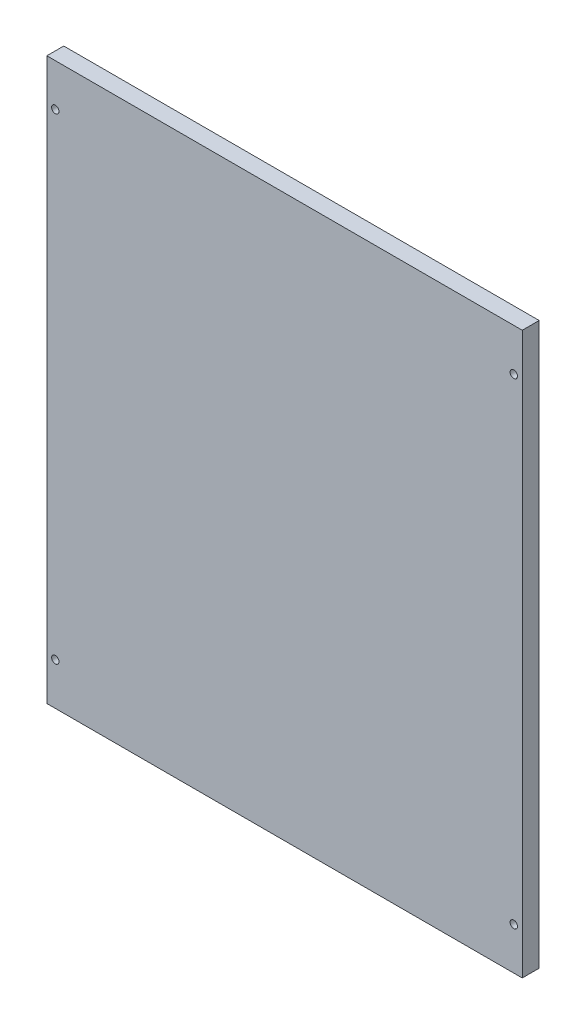
SolidWorks part; units mm, degrees
material "ДСП"
ref_plane "Спереди" through (0, 0, 0) normal (0, 0, 1) x (1, 0, 0)
ref_plane "Сверху" through (0, 0, 0) normal (0, 1, 0) x (1, 0, 0)
ref_plane "Справа" through (0, 0, 0) normal (1, 0, 0) x (0, 0, -1)
sketch "Эскиз1" plane through (0, 0, 0) normal (0, 0, 1) x (1, 0, 0)
  line L1 (0, 0) -> (450, 0)
  line L2 (0, 0) -> (0, 531)
  line L3 (0, 531) -> (450, 531)
  line L4 (450, 0) -> (450, 531)
  dimension "D1" = 531
  dimension "D2" = 450
extrude "Придание толщины" add sketch "Эскиз1" along normal blind 16
sketch "Эскиз3" plane through (0, 0, 16) normal (0, 0, 1) x (1, 0, 0)
  line L0 (0, 531) -> (0, 0) construction
  line L1 (0, 0) -> (450, 0) construction
  circle A0 centre (8, 40) radius 3.5
  dimension "D1" = 7
  dimension "D2" = 8
  dimension "D3" = 40
extrude "Отверстие 1" cut sketch "Эскиз3" against normal blind 16
sketch "Эскиз4" plane through (0, 0, 16) normal (0, 0, 1) x (1, 0, 0)
  line L0 (0, 531) -> (0, 0) construction
  line L1 (0, 0) -> (450, 0) construction
  circle A0 centre (8, 491) radius 3.5
  dimension "D3" = 7
  dimension "D1" = 8
  dimension "D2" = 491
extrude "Отверстие 2" cut sketch "Эскиз4" against normal blind 16
sketch "Эскиз5" plane through (0, 0, 16) normal (0, 0, 1) x (1, 0, 0)
  line L0 (0, 531) -> (0, 0) construction
  line L1 (0, 0) -> (450, 0) construction
  circle A0 centre (442, 40) radius 3.5
  dimension "D1" = 7
  dimension "D3" = 40
  dimension "D2" = 442
extrude "Отверстие 3" cut sketch "Эскиз5" against normal blind 16
sketch "Эскиз6" plane through (0, 0, 16) normal (0, 0, 1) x (1, 0, 0)
  line L0 (0, 531) -> (0, 0) construction
  line L1 (0, 0) -> (450, 0) construction
  circle A0 centre (442, 491) radius 3.5
  dimension "D1" = 7
  dimension "D2" = 442
  dimension "D3" = 491
extrude "Отверстие 4" cut sketch "Эскиз6" against normal blind 16
sketch "Эскиз7" plane through (0, 0, 16) normal (0, 0, 1) x (1, 0, 0)
  line L0 (0, 531) -> (0, 0) construction
  line L1 (0, 0) -> (450, 0) construction
  circle A0 centre (0, 0) radius 4
  dimension "D1" = 8
extrude "Отверстие 5" [suppressed] cut sketch "Эскиз7" against normal blind 16
sketch "Эскиз8" plane through (0, 0, 16) normal (0, 0, 1) x (1, 0, 0)
  line L0 (0, 531) -> (0, 0) construction
  line L1 (0, 0) -> (450, 0) construction
  circle A0 centre (0, 0) radius 4
  dimension "D1" = 8
extrude "Отверстие 6" [suppressed] cut sketch "Эскиз8" against normal blind 16
sketch "Эскиз9" plane through (0, 0, 16) normal (0, 0, 1) x (1, 0, 0)
  line L0 (0, 531) -> (0, 0) construction
  line L1 (0, 0) -> (450, 0) construction
  circle A0 centre (0, 0) radius 4
  dimension "D1" = 8
extrude "Отверстие 7" [suppressed] cut sketch "Эскиз9" against normal blind 16
sketch "Эскиз10" plane through (0, 0, 16) normal (0, 0, 1) x (1, 0, 0)
  line L0 (0, 531) -> (0, 0) construction
  line L1 (0, 0) -> (450, 0) construction
  circle A0 centre (0, 0) radius 4
  dimension "D1" = 8
extrude "Отверстие 8" [suppressed] cut sketch "Эскиз10" against normal blind 16
sketch "Эскиз27" plane through (0, 0, 16) normal (0, 0, 1) x (1, 0, 0)
  line L2 (0, 531) -> (0, 0) construction
  line L3 (0, 0) -> (450, 0) construction
  circle A0 centre (0, 0) radius 4
  dimension "D1" = 8
  dimension "D3" = 0
extrude "Отверстие 9" [suppressed] cut sketch "Эскиз27" against normal blind 10
sketch "Эскиз29" plane through (0, 0, 16) normal (0, 0, 1) x (1, 0, 0)
  line L2 (0, 531) -> (0, 0) construction
  line L3 (0, 0) -> (450, 0) construction
  circle A0 centre (0, 0) radius 4
  dimension "D1" = 8
extrude "Отверстие 10" [suppressed] cut sketch "Эскиз29" against normal blind 10
sketch "Эскиз30" plane through (0, 0, 16) normal (0, 0, 1) x (1, 0, 0)
  line L1 (0, 0) -> (450, 0) construction
  line L3 (0, 531) -> (0, 0) construction
  circle A0 centre (0, 0) radius 4
  dimension "D1" = 8
extrude "Отверстие 11" [suppressed] cut sketch "Эскиз30" against normal blind 10
sketch "Эскиз31" plane through (0, 0, 16) normal (0, 0, 1) x (1, 0, 0)
  line L2 (0, 0) -> (450, 0) construction
  line L3 (0, 531) -> (0, 0) construction
  circle A0 centre (0, 0) radius 4
  dimension "D1" = 8
extrude "Отверстие 12" [suppressed] cut sketch "Эскиз31" against normal blind 10
sketch "Эскиз11" plane through (0, 531, 0) normal (0, 1, 0) x (1, 0, 0)
  line L0 (0, -16) -> (0, 0) construction
  line L1 (450, -16) -> (0, -16) construction
  circle A0 centre (0, -16) radius 2.5
  dimension "D3" = 0
  dimension "D1" = 5
extrude "Отверстие А1" [suppressed] cut sketch "Эскиз11" against normal blind 37
sketch "Эскиз12" plane through (0, 531, 0) normal (0, 1, 0) x (1, 0, 0)
  line L1 (0, -16) -> (0, 0) construction
  line L2 (450, -16) -> (0, -16) construction
  circle A0 centre (0, -16) radius 2.5
  dimension "D3" = 0
  dimension "D1" = 5
extrude "Отверстие А2" [suppressed] cut sketch "Эскиз12" against normal blind 37
sketch "Эскиз13" plane through (0, 531, 0) normal (0, 1, 0) x (1, 0, 0)
  line L1 (0, -16) -> (0, 0) construction
  line L2 (450, -16) -> (0, -16) construction
  circle A0 centre (0, -16) radius 4
  dimension "D1" = 8
  dimension "D3" = 0
extrude "Отверстие А3" [suppressed] cut sketch "Эскиз13" against normal blind 20
sketch "Эскиз14" plane through (0, 531, 0) normal (0, 1, 0) x (1, 0, 0)
  line L0 (0, -16) -> (0, 0) construction
  line L1 (450, -16) -> (0, -16) construction
  circle A0 centre (0, -8) radius 4
  dimension "D1" = 8
  dimension "D3" = 8
extrude "Отверстие А4" [suppressed] cut sketch "Эскиз14" against normal blind 20
sketch "Эскиз15" plane through (450, 0, 0) normal (1, 0, 0) x (0, 0, -1)
  line L0 (-16, 531) -> (0, 531) construction
  line L1 (-16, 0) -> (-16, 531) construction
  circle A0 centre (-16, 531) radius 2.5
  dimension "D2" = 0
  dimension "D3" = 0
  dimension "D1" = 5
extrude "Отверстие В1" [suppressed] cut sketch "Эскиз15" against normal blind 37
sketch "Эскиз16" plane through (450, 0, 0) normal (1, 0, 0) x (0, 0, -1)
  line L0 (-16, 531) -> (0, 531) construction
  line L1 (-16, 0) -> (-16, 531) construction
  circle A0 centre (-16, 531) radius 2.5
  dimension "D1" = 5
extrude "Отверстие В2" [suppressed] cut sketch "Эскиз16" against normal blind 37
sketch "Эскиз17" plane through (450, 0, 0) normal (1, 0, 0) x (0, 0, -1)
  line L1 (-16, 531) -> (0, 531) construction
  line L2 (-16, 0) -> (-16, 531) construction
  circle A0 centre (-16, 531) radius 4
  dimension "D1" = 8
  dimension "D2" = 0
  dimension "D3" = 0
extrude "Отверстие В3" [suppressed] cut sketch "Эскиз17" against normal blind 20
sketch "Эскиз18" plane through (450, 0, 0) normal (1, 0, 0) x (0, 0, -1)
  line L0 (-16, 531) -> (0, 531) construction
  line L1 (-16, 0) -> (-16, 531) construction
  circle A0 centre (-16, 531) radius 4
  dimension "D2" = 8
  dimension "D3" = 0
  dimension "D1" = 0
extrude "Отверстие В4" [suppressed] cut sketch "Эскиз18" against normal blind 20
sketch "Эскиз19" plane through (0, 0, 0) normal (0, -1, 0) x (1, 0, 0)
  line L0 (450, 16) -> (450, 0) construction
  line L1 (0, 16) -> (450, 16) construction
  circle A0 centre (450, 16) radius 2.5
  dimension "D2" = 0
  dimension "D3" = 0
  dimension "D1" = 5
extrude "Отверстие С1" [suppressed] cut sketch "Эскиз19" against normal blind 37
sketch "Эскиз20" plane through (0, 0, 0) normal (0, -1, 0) x (1, 0, 0)
  line L0 (450, 16) -> (450, 0) construction
  line L1 (0, 16) -> (450, 16) construction
  circle A0 centre (450, 16) radius 2.5
  dimension "D3" = 0
  dimension "D1" = 0
  dimension "D2" = 5
extrude "Отверстие С2" [suppressed] cut sketch "Эскиз20" against normal blind 37
sketch "Эскиз21" plane through (0, 0, 0) normal (0, -1, 0) x (1, 0, 0)
  line L0 (450, 16) -> (450, 0) construction
  line L1 (0, 16) -> (450, 16) construction
  circle A0 centre (450, 16) radius 4
  dimension "D1" = 8
  dimension "D2" = 0
  dimension "D3" = 0
extrude "Отверстие С3" [suppressed] cut sketch "Эскиз21" against normal blind 20
sketch "Эскиз22" plane through (0, 0, 0) normal (0, -1, 0) x (1, 0, 0)
  line L0 (450, 16) -> (450, 0) construction
  line L1 (0, 16) -> (450, 16) construction
  circle A0 centre (450, 16) radius 4
  dimension "D1" = 8
  dimension "D2" = 0
  dimension "D3" = 0
extrude "Отверстие С4" [suppressed] cut sketch "Эскиз22" against normal blind 20
sketch "Эскиз23" plane through (0, 0, 0) normal (-1, 0, 0) x (0, 0, 1)
  line L0 (16, 0) -> (0, 0) construction
  line L1 (16, 531) -> (16, 0) construction
  circle A0 centre (16, 0) radius 2.5
  dimension "D2" = 0
  dimension "D3" = 0
  dimension "D1" = 5
extrude "Отверстие Д1" [suppressed] cut sketch "Эскиз23" against normal blind 37
sketch "Эскиз24" plane through (0, 0, 0) normal (-1, 0, 0) x (0, 0, 1)
  line L0 (16, 0) -> (0, 0) construction
  line L1 (16, 531) -> (16, 0) construction
  circle A0 centre (16, 0) radius 2.5
  dimension "D2" = 0
  dimension "D3" = 0
  dimension "D1" = 5
extrude "Отверстие Д2" [suppressed] cut sketch "Эскиз24" against normal blind 37
sketch "Эскиз25" plane through (0, 0, 0) normal (-1, 0, 0) x (0, 0, 1)
  line L0 (16, 0) -> (0, 0) construction
  line L1 (16, 531) -> (16, 0) construction
  circle A0 centre (16, 0) radius 4
  dimension "D1" = 8
  dimension "D2" = 0
  dimension "D3" = 0
extrude "Отверстие Д3" [suppressed] cut sketch "Эскиз25" against normal blind 20
sketch "Эскиз26" plane through (0, 0, 0) normal (-1, 0, 0) x (0, 0, 1)
  line L0 (16, 0) -> (0, 0) construction
  line L1 (16, 531) -> (16, 0) construction
  circle A0 centre (16, 0) radius 4
  dimension "D1" = 8
  dimension "D2" = 0
  dimension "D3" = 0
extrude "Отверстие Д4" [suppressed] cut sketch "Эскиз26" against normal blind 20
equation "\"D1@Придание толщины\" = \"Thick\""
equation "\"D2@Эскиз1\"=\"Width\""
equation "\"D1@Эскиз1\"=\"Height\""
equation "\"D1\" = 7"
equation "\"X1\" = 8"
equation "\"Y1\" = 40"
equation "\"H1\" = 16"
equation "\"D1@Эскиз3\"=\"D1\""
equation "\"D2@Эскиз3\"=\"X1\""
equation "\"D3@Эскиз3\"=\"Y1\""
equation "\"D1@Отверстие 1\"=\"H1\""
equation "\"D2\" = 7"
equation "\"X2\" = 8"
equation "\"Y2\" = 491"
equation "\"H2\" = 16"
equation "\"D3\" = 7"
equation "\"X3\" = 442"
equation "\"Y3\" = 40"
equation "\"H3\" = 16"
equation "\"D4\" = 7"
equation "\"X4\" = 442"
equation "\"Y4\" = 491"
equation "\"H4\" = 16"
equation "\"D5\" = 0"
equation "\"X5\" = 0"
equation "\"Y5\" = 0"
equation "\"H5\" = 0"
equation "\"D6\" = 0"
equation "\"X6\" = 0"
equation "\"Y6\" = 0"
equation "\"H6\" = 0"
equation "\"D7\" = 0"
equation "\"X7\" = 0"
equation "\"Y7\" = 0"
equation "\"H7\" = 0"
equation "\"D8\" = 0"
equation "\"X8\" = 0"
equation "\"Y8\" = 0"
equation "\"H8\" = 0"
equation "\"D3@Эскиз4\"=\"D2\""
equation "\"D1@Эскиз4\"=\"X2\""
equation "\"D2@Эскиз4\"=\"Y2\""
equation "\"D1@Отверстие 2\"=\"H2\""
equation "\"D2@Эскиз5\"=\"X3\""
equation "\"D1@Эскиз5\"=\"D3\""
equation "\"D3@Эскиз5\"=\"Y3\""
equation "\"D1@Отверстие 3\" = \"H3\""
equation "\"D1@Эскиз6\"=\"D4\""
equation "\"D2@Эскиз6\"=\"X4\""
equation "\"D3@Эскиз6\"=\"Y4\""
equation "\"D1@Отверстие 4\" = \"H4\""
equation "\"D1@Эскиз7\"=\"D5\""
equation "\"D2@Эскиз7\"=\"X5\""
equation "\"D3@Эскиз7\"=\"Y5\""
equation "\"D1@Отверстие 5\" = \"H5\""
equation "\"D1@Эскиз8\"=\"D6\""
equation "\"D2@Эскиз8\"=\"X6\""
equation "\"D3@Эскиз8\"=\"Y6\""
equation "\"D1@Отверстие 6\" = \"H6\""
equation "\"D1@Эскиз9\"=\"D7\""
equation "\"D2@Эскиз9\"=\"X7\""
equation "\"D3@Эскиз9\"=\"Y7\""
equation "\"D1@Отверстие 7\" = \"H7\""
equation "\"D1@Эскиз10\"=\"D8\""
equation "\"D2@Эскиз10\"=\"X8\""
equation "\"D3@Эскиз10\"=\"Y8\""
equation "\"D1@Отверстие 8\" = \"H8\""
equation "\"Отверстие 1\"= IIF ( \"D1\" = 0 , \"suppressed\" , \"unsuppressed\" )"
equation "\"Отверстие 2\"= IIF ( \"D2\" = 0 , \"suppressed\" , \"unsuppressed\" )"
equation "\"Отверстие 3\"= IIF ( \"D3\" = 0 , \"suppressed\" , \"unsuppressed\" )"
equation "\"Отверстие 4\"= IIF ( \"D4\" = 0 , \"suppressed\" , \"unsuppressed\" )"
equation "\"Отверстие 5\"= IIF ( \"D5\" = 0 , \"suppressed\" , \"unsuppressed\" )"
equation "\"Отверстие 6\" = IIF ( \"D6\" = 0 , \"suppressed\" , \"unsuppressed\" )"
equation "\"Отверстие 7\"= IIF ( \"D7\" = 0 , \"suppressed\" , \"unsuppressed\" )"
equation "\"Отверстие 8\"= IIF ( \"D8\" = 0 , \"suppressed\" , \"unsuppressed\" )"
equation "\"DA1\" = 0"
equation "\"XA1\" = 0"
equation "\"YA1\" = 0"
equation "\"HA1\" = 0"
equation "\"DA2\" = 0"
equation "\"XA2\" = 0"
equation "\"YA2\" = 0"
equation "\"HA2\" = 0"
equation "\"DA3\" = 0"
equation "\"XA3\" = 0"
equation "\"YA3\" = 0"
equation "\"DA4\" = 0"
equation "\"XA4\" = 0"
equation "\"YA4\" = 0"
equation "\"HA4\" = 0"
equation "\"D1@Эскиз11\"=\"DA1\""
equation "\"D2@Эскиз11\"=\"XA1\""
equation "\"D3@Эскиз11\"=\"YA1\""
equation "\"D1@Отверстие А1\" = \"HA1\""
equation "\"D1@Эскиз12\"=\"DA2\""
equation "\"D2@Эскиз12\"=\"XA2\""
equation "\"HA3\" = 0"
equation "\"D1@Эскиз13\"=\"DA3\""
equation "\"D2@Эскиз13\"=\"XA3\""
equation "\"D3@Эскиз13\"=\"YA3\""
equation "\"D1@Отверстие А3\" = \"HA3\""
equation "\"D1@Отверстие А2\" = \"HA2\""
equation "\"D1@Эскиз14\"=\"DA4\""
equation "\"D2@Эскиз14\"=\"XA4\""
equation "\"Отверстие А1\"= IIF ( \"DA1\" = 0 , \"suppressed\" , \"unsuppressed\" )"
equation "\"Отверстие А2\"= IIF ( \"DA2\" = 0 , \"suppressed\" , \"unsuppressed\" )"
equation "\"Отверстие А3\"= IIF ( \"DA3\" = 0 , \"suppressed\" , \"unsuppressed\" )"
equation "\"Отверстие А4\"= IIF ( \"DA4\" = 0 , \"suppressed\" , \"unsuppressed\" )"
equation "\"DB1\" = 0"
equation "\"XB1\" = 0"
equation "\"YB1\" = 0"
equation "\"HB1\" = 0"
equation "\"DB2\" = 0"
equation "\"XB2\" = 0"
equation "\"YB2\" = 0"
equation "\"HB2\" = 0"
equation "\"DB3\" = 0"
equation "\"XB3\" = 0"
equation "\"YB3\" = 0"
equation "\"HB3\" = 0"
equation "\"DB4\" = 0"
equation "\"XB4\" = 0"
equation "\"YB4\" = 0"
equation "\"HB4\" = 0"
equation "\"DC1\" = 0"
equation "\"XC1\" = 0"
equation "\"YC1\" = 0"
equation "\"HC1\" = 0"
equation "\"DC2\" = 0"
equation "\"XC2\" = 0"
equation "\"YC2\" = 0"
equation "\"HC2\" = 0"
equation "\"DC3\" = 0"
equation "\"XC3\" = 0"
equation "\"YC3\" = 0"
equation "\"HC3\" = 0"
equation "\"DC4\" = 0"
equation "\"XC4\" = 0"
equation "\"YC4\" = 0"
equation "\"HC4\" = 0"
equation "\"DD1\" = 0"
equation "\"XD1\" = 0"
equation "\"YD1\" = 0"
equation "\"HD1\" = 0"
equation "\"DD2\" = 0"
equation "\"XD2\" = 0"
equation "\"YD2\" = 0"
equation "\"HD2\" = 0"
equation "\"DD3\" = 0"
equation "\"XD3\" = 0"
equation "\"YD3\" = 0"
equation "\"HD3\" = 0"
equation "\"DD4\" = 0"
equation "\"XD4\" = 0"
equation "\"YD4\" = 0"
equation "\"HD4\" = 0"
equation "\"D1@Эскиз15\"=\"DB1\""
equation "\"D2@Эскиз15\"=\"XB1\""
equation "\"D3@Эскиз15\"=\"YB1\""
equation "\"D1@Отверстие В1\" = \"HB1\""
equation "\"D1@Эскиз16\"=\"DB2\""
equation "\"D2@Эскиз16\"=\"XB2\""
equation "\"D3@Эскиз16\"=\"YB2\""
equation "\"D1@Отверстие В2\" = \"HB2\""
equation "\"D1@Эскиз17\"=\"DB3\""
equation "\"D2@Эскиз17\"=\"XB3\""
equation "\"D3@Эскиз17\"=\"YB3\""
equation "\"D1@Отверстие В3\" = \"HB3\""
equation "\"D1@Эскиз18\"=\"XB4\""
equation "\"D2@Эскиз18\"=\"DB4\""
equation "\"D3@Эскиз18\"=\"YB4\""
equation "\"D1@Отверстие В4\" = \"HB4\""
equation "\"D1@Эскиз19\"=\"DC1\""
equation "\"D2@Эскиз19\"=\"XC1\""
equation "\"D3@Эскиз19\"=\"YC1\""
equation "\"D1@Отверстие С1\" = \"HC1\""
equation "\"D1@Эскиз20\"=\"XC2\""
equation "\"D2@Эскиз20\"=\"DC2\""
equation "\"D3@Эскиз20\"=\"YC2\""
equation "\"D1@Отверстие С2\" = \"HC2\""
equation "\"D1@Эскиз21\"=\"DC3\""
equation "\"D2@Эскиз21\"=\"XC3\""
equation "\"D3@Эскиз21\"=\"YC3\""
equation "\"D1@Отверстие С3\" = \"HC3\""
equation "\"D1@Эскиз22\"=\"DC4\""
equation "\"D2@Эскиз22\"=\"XC4\""
equation "\"D3@Эскиз22\"=\"YC4\""
equation "\"D1@Отверстие С4\" = \"HC4\""
equation "\"D1@Эскиз23\"=\"DD1\""
equation "\"D2@Эскиз23\"=\"XD1\""
equation "\"D3@Эскиз23\"=\"YD1\""
equation "\"D1@Отверстие Д1\" = \"HD1\""
equation "\"D1@Эскиз24\"=\"DD2\""
equation "\"D2@Эскиз24\"=\"XD2\""
equation "\"D3@Эскиз24\"=\"YD2\""
equation "\"D1@Отверстие Д2\" = \"HD2\""
equation "\"D1@Эскиз25\"=\"DD3\""
equation "\"D2@Эскиз25\"=\"XD3\""
equation "\"D3@Эскиз25\"=\"YD3\""
equation "\"D1@Отверстие Д3\" = \"HD3\""
equation "\"D1@Эскиз26\"=\"DD4\""
equation "\"D2@Эскиз26\"=\"XD4\""
equation "\"D3@Эскиз26\"=\"YD4\""
equation "\"D1@Отверстие Д4\" = \"HD4\""
equation "\"Отверстие В1\"= IIF ( \"DB1\" = 0 , \"suppressed\" , \"unsuppressed\" )"
equation "\"Отверстие В2\"= IIF ( \"DB2\" = 0 , \"suppressed\" , \"unsuppressed\" )"
equation "\"Отверстие В3\"= IIF ( \"DB3\" = 0 , \"suppressed\" , \"unsuppressed\" )"
equation "\"Отверстие В4\"= IIF ( \"DB4\" = 0 , \"suppressed\" , \"unsuppressed\" )"
equation "\"Отверстие С1\"= IIF ( \"DC1\" = 0 , \"suppressed\" , \"unsuppressed\" )"
equation "\"Отверстие С2\"= IIF ( \"DC2\" = 0 , \"suppressed\" , \"unsuppressed\" )"
equation "\"Отверстие С3\"= IIF ( \"DC3\" = 0 , \"suppressed\" , \"unsuppressed\" )"
equation "\"Отверстие С4\"= IIF ( \"DC4\" = 0 , \"suppressed\" , \"unsuppressed\" )"
equation "\"Отверстие Д1\"= IIF ( \"DD1\" = 0 , \"suppressed\" , \"unsuppressed\" )"
equation "\"Отверстие Д2\"= IIF ( \"DD2\" = 0 , \"suppressed\" , \"unsuppressed\" )"
equation "\"Отверстие Д3\"= IIF ( \"DD3\" = 0 , \"suppressed\" , \"unsuppressed\" )"
equation "\"Отверстие Д4\"= IIF ( \"DD4\" = 0 , \"suppressed\" , \"unsuppressed\" )"
equation "\"D9\" = 0"
equation "\"X9\" = 0"
equation "\"Y9\" = 0"
equation "\"H9\" = 0"
equation "\"D10\" = 0"
equation "\"X10\" = 0"
equation "\"Y10\" = 0"
equation "\"H10\" = 0"
equation "\"D11\" = 0"
equation "\"X11\" = 0"
equation "\"Y11\" = 0"
equation "\"H11\" = 0"
equation "\"D12\" = 0"
equation "\"X12\" = 0"
equation "\"Y12\" = 0"
equation "\"H12\" = 0"
equation "\"D1@Эскиз27\"=\"D9\""
equation "\"D2@Эскиз27\"=\"X9\""
equation "\"D3@Эскиз27\"=\"Y9\""
equation "\"D1@Отверстие 9\" = \"H9\""
equation "\"D1@Эскиз29\"=\"D10\""
equation "\"D2@Эскиз29\"=\"X10\""
equation "\"D3@Эскиз29\"=\"Y10\""
equation "\"D1@Отверстие 10\" = \"H10\""
equation "\"D1@Эскиз30\"=\"D11\""
equation "\"D2@Эскиз30\"=\"X11\""
equation "\"D3@Эскиз30\"=\"Y11\""
equation "\"D1@Отверстие 11\" = \"H11\""
equation "\"D1@Эскиз31\"=\"D12\""
equation "\"D2@Эскиз31\"=\"X12\""
equation "\"D3@Эскиз31\"=\"Y12\""
equation "\"D1@Отверстие 12\" = \"H12\""
equation "\"Отверстие 9\"= IIF ( \"D9\" = 0 , \"suppressed\" , \"unsuppressed\" )"
equation "\"Отверстие 10\"= IIF ( \"D10\" = 0 , \"suppressed\" , \"unsuppressed\" )"
equation "\"Отверстие 11\"= IIF ( \"D11\" = 0 , \"suppressed\" , \"unsuppressed\" )"
equation "\"Отверстие 12\"= IIF ( \"D12\" = 0 , \"suppressed\" , \"unsuppressed\" )"
equation "\"Height\" = 531"
equation "\"Width\" = 450"
equation "\"Thick\" = 16"
equation "\"D3@Эскиз12\"=\"YA2\""
